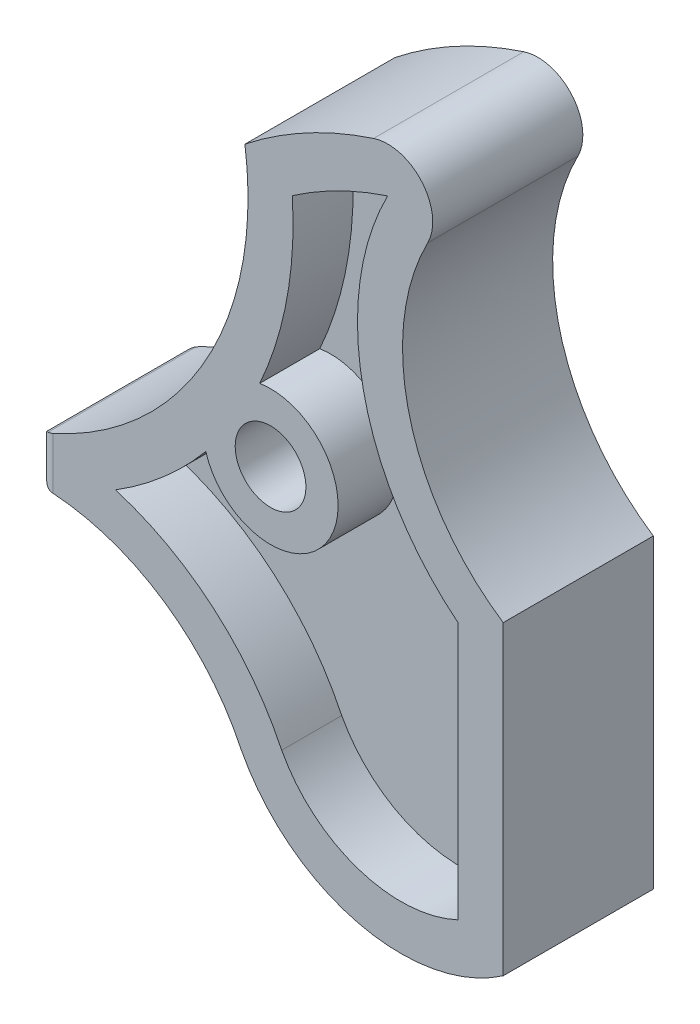
SolidWorks part; units mm, degrees
ref_plane "Alzado" through (0, 0, 0) normal (0, 0, 1) x (1, 0, 0)
ref_plane "Planta" through (0, 0, 0) normal (0, 1, 0) x (1, 0, 0)
ref_plane "Vista lateral" through (0, 0, 0) normal (1, 0, 0) x (0, 0, -1)
sketch "Croquis1" plane through (0, 0, 0) normal (0, 0, 1) x (1, 0, 0)
  line L1 (-15.5, -23.75) -> (15.5, -23.75)
  line L2 (-15.5, -23.75) -> (-15.5, 23.75)
  line L3 (-15.5, 23.75) -> (15.5, 23.75)
  line L4 (15.5, -23.75) -> (15.5, 23.75)
  line L5 (-15.5, -23.75) -> (15.5, 23.75) construction
  line L6 (-15.5, 23.75) -> (15.5, -23.75) construction
  circle A0 centre (0, 0) radius 1.5
  dimension "D1" = 3
  dimension "D2" = 47.5
  dimension "D3" = 31
extrude "Saliente-Extruir1" add sketch "Croquis1" along normal mid plane 10
sketch "Croquis2" plane through (0, 0, 5) normal (0, 0, 1) x (1, 0, 0)
  line L0 (-15.5, -8.75) -> (63.2071, -8.75) construction
  line L4 (15.5, -23.75) -> (15.5, 23.75)
  line L5 (15.5, 23.75) -> (-15.5, 23.75)
  line L6 (-15.5, 23.75) -> (-15.5, -23.75)
  line L7 (-15.5, -23.75) -> (15.5, -23.75)
  line L8 (15.5, -23.75) -> (15.5, 23.75)
  line L9 (15.5, 23.75) -> (-15.5, 23.75)
  line L10 (-15.5, 23.75) -> (-15.5, -23.75)
  line L11 (-15.5, -23.75) -> (15.5, -23.75)
  circle A0 centre (-15.5, -23.75) radius 15
  arc A1 (-1.9396, -17.3378) -> (15.5, -21.6236) centre (8.68, -11.75) ccw
  arc A2 (15.5, 23.75) -> (15.5, -1.25) centre (23.7916, 11.25) ccw
  arc A3 (-15.5, -5.75) -> (-1.7063, 17.75) centre (-23.5, 14.7439) ccw
  arc A4 (-1.7063, 17.75) -> (15.5, 23.75) centre (15.5, -3.9215) cw
  line M5 (15.5, -23.75) -> (15.5, 23.75)
  line M6 (15.5, 23.75) -> (-15.5, 23.75)
  line M7 (-15.5, 23.75) -> (-15.5, -23.75)
  line M8 (-15.5, -23.75) -> (15.5, -23.75)
  dimension "D2" = 30
  dimension "D3" = 25
  dimension "D4" = 15
  dimension "D5" = 12
  dimension "D9" = 22
  dimension "D6" = 6.82
  dimension "D7" = 3
  dimension "D8" = 6
  dimension "D10" = 8
  dimension "D1" = 0
extrude "Cortar-Extruir1" cut sketch "Croquis2" against normal blind 10 contours A0 L10 M8 | A1 A0 L11 | A1 M8 M5 | A3 A4 M6 M7 | A2 M5 region at (13.8267, -23.1231, 5) region at (1.4464, -22.26, 5) region at (12.7575, 11.25, 5) region at (-9.1338, -17.3838, 5) region at (-8.2316, 12.2777, 5)
sketch "Croquis4" plane through (0, 0, 5) normal (0, 0, 1) x (1, 0, 0)
  line L2 (15.5, -21.6236) -> (15.5, -1.25)
  line L3 (-15.5, -5.75) -> (-15.5, -8.75)
  line L4 (15.5, -21.6236) -> (15.5, -1.25)
  line L5 (-15.5, -5.75) -> (-15.5, -8.75)
  line L8 (12.5, -19.8991) -> (12.5, -2.7679)
  line L9 (12.5, -19.8991) -> (12.5, -2.7679)
  arc A5 (-1.9396, -17.3378) -> (15.5, -21.6236) centre (8.68, -11.75) ccw
  arc A6 (15.5, 23.75) -> (15.5, -1.25) centre (23.7916, 11.25) ccw
  arc A7 (15.5, 23.75) -> (-1.7063, 17.75) centre (15.5, -3.9215) ccw
  arc A8 (-15.5, -5.75) -> (-1.7063, 17.75) centre (-23.5, 14.7439) ccw
  arc A9 (-1.9396, -17.3378) -> (-15.5, -8.75) centre (-15.5, -23.75) ccw
  arc A10 (-1.9396, -17.3378) -> (15.5, -21.6236) centre (8.68, -11.75) ccw
  arc A11 (15.5, 23.75) -> (15.5, -1.25) centre (23.7916, 11.25) ccw
  arc A12 (15.5, 23.75) -> (-1.7063, 17.75) centre (15.5, -3.9215) ccw
  arc A13 (-15.5, -5.75) -> (-1.7063, 17.75) centre (-23.5, 14.7439) ccw
  arc A14 (-1.9396, -17.3378) -> (-15.5, -8.75) centre (-15.5, -23.75) ccw
  arc A20 (0.7418, -15.9908) -> (12.5, -19.8991) centre (8.68, -11.75) ccw
  arc A21 (7.8032, 19.5187) -> (12.5, -2.7679) centre (23.7916, 11.25) ccw
  arc A22 (7.8032, 19.5187) -> (1.4479, 16.3571) centre (15.5, -3.9215) ccw
  arc A23 (-10.3328, -6.5076) -> (1.4479, 16.3571) centre (-23.5, 14.7439) ccw
  arc A24 (0.7418, -15.9908) -> (-10.3328, -6.5076) centre (-15.5, -23.75) ccw
  arc A25 (0.7418, -15.9908) -> (12.5, -19.8991) centre (8.68, -11.75) ccw
  arc A26 (7.8032, 19.5187) -> (12.5, -2.7679) centre (23.7916, 11.25) ccw
  arc A27 (7.8032, 19.5187) -> (1.4479, 16.3571) centre (15.5, -3.9215) ccw
  arc A28 (-10.3328, -6.5076) -> (1.4479, 16.3571) centre (-23.5, 14.7439) ccw
  arc A29 (0.7418, -15.9908) -> (-10.3328, -6.5076) centre (-15.5, -23.75) ccw
  circle M21 centre (0, 0) radius 1.5
  dimension "D1" = 0
  dimension "D2" = 3
extrude "Cortar-Extruir2" cut sketch "Croquis4" against normal blind 4 contours A29 A25 L9 A26 A27 A28 M21 region at (4.0436, -4.6033, 5)
mirror "Simetría1" about plane through (0, 0, 0) normal (0, 0, 1) of "Cortar-Extruir2"
sketch "Croquis5" plane through (0, 0, 1) normal (0, 0, 1) x (1, 0, 0)
  circle A0 centre (0, 0) radius 1.5 construction
  circle A1 centre (0, 0) radius 1.5
  circle A2 centre (0, 0) radius 2.355
  circle A3 centre (0, 0) radius 4.5
  arc M6 (1.4479, 16.3571) -> (-10.3328, -6.5076) centre (-23.5, 14.7439) cw
  dimension "D1" = 4.71
  dimension "D2" = 9
extrude "Saliente-Extruir2" add sketch "Croquis5" along normal up to surface (4 mm away) and the other way up to surface (6 mm away) contours A3 A2 M6 region at (0.6302, -4.3284, 1) up to face at (1.285, -2.3005, 5) other way up to face at (3.9937, -2.1171, -5)
fillet "Redondeo1" radius 3 1 edges at (15.5, 23.75, 0)
fillet "Redondeo2" radius 1 4 edges at (-15.5, -8.75, 0) (-15.5, -7.25, -5) (-15.5, -5.75, 0) (-15.5, -7.25, 5)
